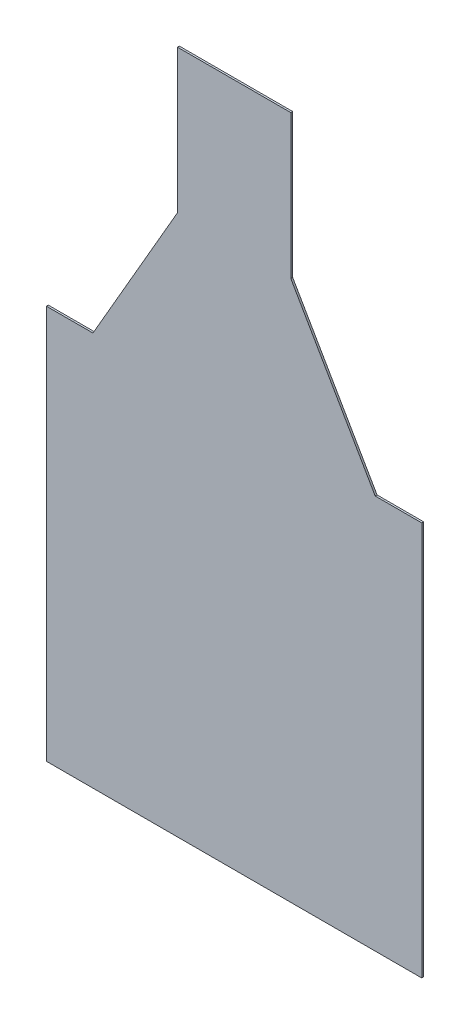
SolidWorks part; units mm, degrees
ref_plane "Front Plane" through (0, 0, 0) normal (0, 0, 1) x (1, 0, 0)
ref_plane "Top Plane" through (0, 0, 0) normal (0, 1, 0) x (1, 0, 0)
ref_plane "Right Plane" through (0, 0, 0) normal (1, 0, 0) x (0, 0, -1)
sketch "Sketch2" plane through (0, 0, 0) normal (0, 0, 1) x (1, 0, 0)
  line L0 (200, 218.5754) -> (-200, 218.5754) construction
  line L1 (-200, 238.5754) -> (200, 238.5754)
  line L2 (-200, 238.5754) -> (-200, -181.4246)
  line L3 (-200, -181.4246) -> (200, -181.4246)
  line L4 (200, 238.5754) -> (200, -181.4246)
  line L5 (-200, 238.5754) -> (200, -181.4246) construction
  line L6 (-200, -181.4246) -> (200, 238.5754) construction
  point P0 (0, 0)
  dimension "D1" = 20
sheet metal parameters "Sheet-Metal1" thickness 2 parameters "D1"=0.7366
base flange "Base-Flange1" sketch "Sketch2" thickness 2 reverse thickness direction no parameters "D1"=0.7366
sketch "Sketch5" plane through (0, 0, 0) normal (0, 0, 1) x (1, 0, 0)
  line L0 (0, 238.5754) -> (0, 547.4306) construction
  line L1 (200, 238.5754) -> (-200, 238.5754) construction
  line L2 (-60.4218, 394.3765) -> (-60.4218, 547.4306)
  line L3 (-60.4218, 394.3765) -> (-150.3736, 238.5754)
  line L4 (-150.3736, 238.5754) -> (150.3736, 238.5754)
  line L5 (60.4218, 394.3765) -> (150.3736, 238.5754)
  line L6 (-60.4218, 547.4306) -> (60.4218, 547.4306)
  line L7 (60.4218, 394.3765) -> (60.4218, 547.4306)
  dimension "D1" = 60
base flange "Tab1" sketch "Sketch5" thickness 2 reverse thickness direction no parameters "D1"=0.7366
flat pattern "Flat-Pattern1" [suppressed]
sketch "Bend-Lines1" plane through (0, 0, 0) normal (0, 1, 0) x (1, 0, 0)
sketch3d "Bounding-Box1" [suppressed]
  line L0 (-42.963, 53.0691, 0) -> (-42.963, -53.0691, 0) construction
  line L1 (42.963, 53.0691, 0) -> (42.963, -53.0691, 0) construction
  line L2 (-42.963, 53.0691, 0) -> (42.963, 53.0691, 0) construction
  line L3 (-42.963, -53.0691, 0) -> (42.963, -53.0691, 0) construction
